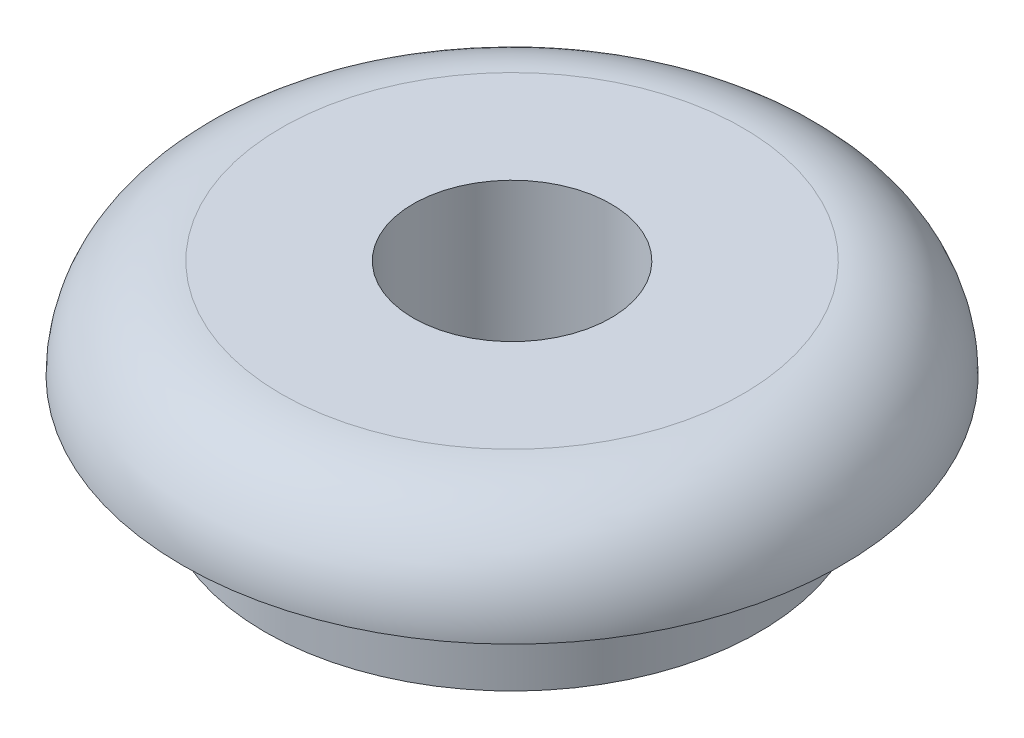
SolidWorks part; units mm, degrees
ref_plane "Front Plane" through (0, 0, 0) normal (0, 0, 1) x (1, 0, 0)
ref_plane "Top Plane" through (0, 0, 0) normal (0, 1, 0) x (1, 0, 0)
ref_plane "Right Plane" through (0, 0, 0) normal (1, 0, 0) x (0, 0, -1)
sketch "Sketch1" plane through (0, 0, 0) normal (0, 1, 0) x (1, 0, 0)
  circle A0 centre (0, 0) radius 7.5
  dimension "D1" = 15
extrude "Boss-Extrude1" add sketch "Sketch1" along normal blind 6
sketch "Sketch2" plane through (0, 6, 0) normal (0, 1, 0) x (1, 0, 0)
  circle A0 centre (0, 0) radius 10
  circle A1 centre (0, 0) radius 7.5
  circle A2 centre (0, 0) radius 7.5 construction
  dimension "D1" = 20
extrude "Boss-Extrude2" add sketch "Sketch2" against normal blind 3
fillet "Fillet1" radius 3 1 edges at (0, 6, 10)
sketch "Sketch3" plane through (0, 6, 0) normal (0, 1, 0) x (1, 0, 0)
  line L0 (0, 7) -> (0, -7) construction
  circle A0 centre (0, 0) radius 7 construction
  circle A1 centre (0, 0) radius 3
extrude "Cut-Extrude1" cut sketch "Sketch3" against normal through all
